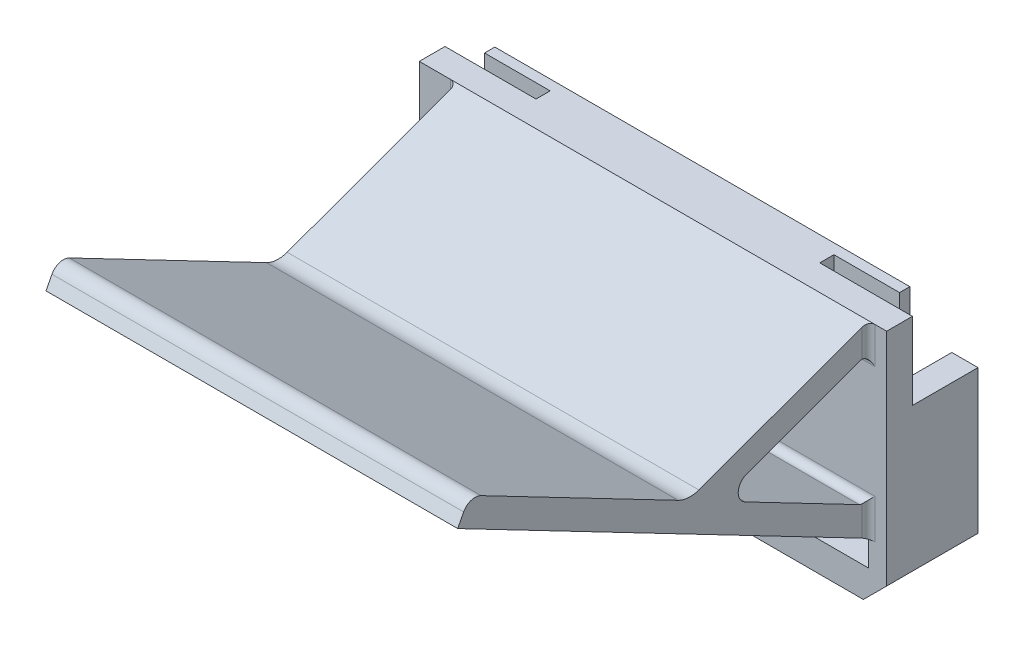
SolidWorks part; units mm, degrees
ref_plane "前视基准面" through (0, 0, 0) normal (0, 0, 1) x (1, 0, 0)
ref_plane "上视基准面" through (0, 0, 0) normal (0, 1, 0) x (1, 0, 0)
ref_plane "右视基准面" through (0, 0, 0) normal (1, 0, 0) x (0, 0, -1)
sketch "草图1" plane through (0, 0, 0) normal (0, 0, 1) x (1, 0, 0)
  line L1 (18.2273, -16.15) -> (18.2273, -27.3069)
  line L2 (-18.1003, -16.15) -> (-18.1003, -26.7989)
  line L5 (16.1905, -16.15) -> (16.1905, -25.7989)
  line L6 (-18.1003, -16.15) -> (-15.8095, -16.15)
  line L7 (16.1905, -16.15) -> (18.2273, -16.15)
  line L66 (-18.1003, -26.7989) -> (-15.7818, -29.1173)
  line L67 (-15.7818, -29.1173) -> (5.5542, -29.1173)
  line L71 (5.5542, -29.1173) -> (16.4168, -29.1173)
  line L72 (16.4168, -29.1173) -> (18.2273, -27.3069)
  line L749 (15.1905, -26.7989) -> (-14.8095, -26.7989)
  line L751 (-15.8095, -25.7989) -> (-15.8095, -16.15)
  arc A51 (15.1905, -26.7989) -> (16.1905, -25.7989) centre (15.1905, -25.7989) ccw
  arc A53 (-15.8095, -25.7989) -> (-14.8095, -26.7989) centre (-14.8095, -25.7989) ccw
  point P16 (-15.8095, -16.0548)
extrude "凸台-拉伸1" add sketch "草图1" along normal up to surface (7.1 mm away)
sketch "草图2" plane through (0, -16.15, 0) normal (0, 1, 0) x (1, 0, 0)
  line L24 (16.1273, -4) -> (16.1273, -3.2)
  line L25 (11.0273, -4) -> (16.1273, -4)
  line L26 (11.0273, -5.1) -> (11.0273, -4)
  line L27 (18.2273, -5.1) -> (11.0273, -5.1)
  line L28 (18.2273, -7.1) -> (18.2273, -5.1)
  line L29 (-18.1003, -7.1) -> (18.2273, -7.1)
  line L30 (-18.1003, -5.1) -> (-18.1003, -7.1)
  line L31 (-11.0273, -5.1) -> (-18.1003, -5.1)
  line L32 (-11.0273, -4) -> (-11.0273, -5.1)
  line L33 (-16.1278, -4) -> (-11.0273, -4)
  line L34 (-16.1278, -3.2) -> (-16.1278, -4)
  line L35 (16.1273, -3.2) -> (-16.1278, -3.2)
extrude "凸台-拉伸2" add sketch "草图2" along normal offset from surface 0.15 and the other way up to next
sketch "草图3" plane through (0, 0, 7.1) normal (0, 0, 1) x (1, 0, 0)
  line L0 (0.3175, -29.1173) -> (0.3175, -21.7075) construction
  line L3 (16.8175, -24.7989) -> (-15.1825, -24.7989)
  line L4 (16.8175, -24.7989) -> (16.8175, -26.7989)
  line L5 (16.8175, -26.7989) -> (-15.1825, -26.7989)
  line L6 (-15.1825, -24.7989) -> (-15.1825, -26.7989)
  point P8 (0, 0)
  dimension "D1" = 2
  dimension "D2" = 32
  dimension "D3" = 15.5
extrude "切除-拉伸1" cut sketch "草图3" against normal through all
sketch "草图4" plane through (0, -29.1173, 0) normal (0, -1, 0) x (1, 0, 0)
  line L4 (-15.1825, 5.1) -> (-15.8095, 5.1)
  line L5 (-15.1825, 4) -> (-15.1825, 5.1)
  line L6 (-15.8095, 4) -> (-15.1825, 4)
  line L7 (-15.8095, 5.1) -> (-15.8095, 4)
  line L8 (-15.1825, 5.1) -> (-15.8095, 5.1)
  line L9 (-15.1825, 4) -> (-15.1825, 5.1)
  line L10 (-15.8095, 4) -> (-15.1825, 4)
  line L11 (-15.8095, 5.1) -> (-15.8095, 4)
  dimension "D1" = 0
extrude "凸台-拉伸3" add sketch "草图4" against normal up to surface (4.3185 mm away)
sketch "草图5" plane through (-15.1825, 0, 0) normal (1, 0, 0) x (0, 0, -1)
  line L0 (-7.1, -24.7989) -> (-39.0324, -8.1759)
  line L1 (-7.1, -10.15) -> (-7.1, -27.3069) construction
  line L2 (-39.0324, -8.1759) -> (-38.5706, -7.2889)
  line L3 (-37.2219, -6.8636) -> (-21.8925, -14.8436)
  line L4 (-7.1, -22.5441) -> (-7.1, -24.7989)
  line L5 (-7.1, -10.15) -> (-20.285, -14.9489)
  line L6 (-7.1, -12.2784) -> (-16.5702, -15.7252)
  line L7 (-16.6899, -17.5519) -> (-7.1, -22.5441)
  line L8 (-7.1, -10.15) -> (-7.1, -12.2784)
  arc A0 (-38.5706, -7.2889) -> (-37.2219, -6.8636) centre (-37.6836, -7.7506) cw
  arc A1 (-16.5702, -15.7252) -> (-16.6899, -17.5519) centre (-16.2281, -16.6649) ccw
  arc A2 (-20.285, -14.9489) -> (-21.8925, -14.8436) centre (-20.969, -13.0696) cw
  point P14 (-38.1089, -6.4019)
  point P18 (-18.7058, -16.5025)
  dimension "D3" = 2
  dimension "D6" = 1
  dimension "D7" = 1
  dimension "D8" = 2
  dimension "D1" = 62.5
  dimension "D2" = 36
  dimension "D4" = 70
  dimension "D5" = 2
extrude "凸台-拉伸4" add sketch "草图5" along normal up to surface (32 mm away) up to face at (16.8175, -25.7989, 3.55)
fillet "圆角1" radius 0.5 7 edges at (0.8175, -12.2784, 7.1) (-15.1825, -11.2142, 7.1) (-15.1825, -23.6715, 7.1) (16.8175, -23.6715, 7.1) (0.8175, -22.5441, 7.1) (16.8175, -11.2142, 7.1) (0.4724, -24.7989, 3.2)
